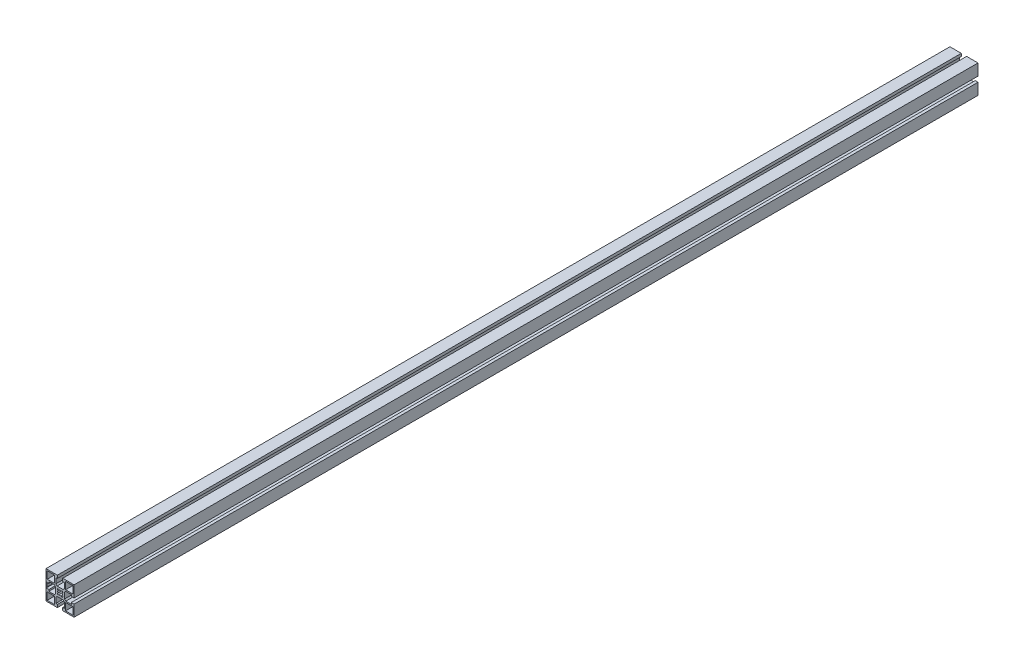
SolidWorks part; units mm, degrees
material "6061 Alloy"
ref_plane "Front Plane" through (0, 0, 0) normal (0, 0, 1) x (1, 0, 0)
ref_plane "Top Plane" through (0, 0, 0) normal (0, 1, 0) x (1, 0, 0)
ref_plane "Right Plane" through (0, 0, 0) normal (1, 0, 0) x (0, 0, -1)
sketch "Sketch1" plane through (0, 0, 0) normal (0, 0, 1) x (1, 0, 0)
  line L0 (-4.2495, 22.1993) -> (-4.2495, 22.4993)
  line L1 (-4.2495, 22.4993) -> (-4.2495, 22.1993)
  line L2 (4.2505, 22.1993) -> (4.2505, 22.4993)
  line L3 (4.2505, 22.4993) -> (4.2505, 22.1993)
  line L4 (-22.1995, 4.2493) -> (-22.4995, 4.2493)
  line L5 (-22.1995, -4.2507) -> (-22.4995, -4.2507)
  line L6 (-4.2495, -22.2007) -> (-4.2495, -22.5007)
  line L7 (4.2505, -22.2007) -> (4.2505, -22.5007)
  line L8 (-22.4995, -22.5007) -> (22.5005, -22.5007)
  line L9 (22.5005, -22.5007) -> (22.5005, 22.4993)
  line L10 (22.5005, 22.4993) -> (-22.4995, 22.4993)
  line L11 (-22.4995, 22.4993) -> (-22.4995, -22.5007)
  line L12 (22.2005, -4.2507) -> (22.5005, -4.2507)
  line L13 (22.2005, 4.2493) -> (22.5005, 4.2493)
  line L24 (-20.4995, -20.5007) -> (-20.4995, -8.8007)
  line L25 (-8.7996, -20.5007) -> (-20.4995, -20.5007)
  line L26 (-8.7996, -8.8007) -> (-8.7996, -20.5007)
  line L27 (-20.4995, -8.8007) -> (-8.7996, -8.8007)
  line L28 (8.8005, -20.5008) -> (8.8005, -8.8008)
  line L29 (20.5005, -20.5008) -> (8.8005, -20.5008)
  line L30 (20.5005, -8.8008) -> (20.5005, -20.5008)
  line L31 (8.8005, -8.8008) -> (20.5005, -8.8008)
  line L32 (20.5006, 8.7993) -> (8.8006, 8.7993)
  line L33 (20.5006, 20.4993) -> (20.5006, 8.7993)
  line L34 (8.8006, 20.4993) -> (20.5006, 20.4993)
  line L35 (8.8006, 8.7993) -> (8.8006, 20.4993)
  line L36 (-8.7995, 20.4993) -> (-8.7995, 8.7993)
  line L37 (-8.7995, 8.7993) -> (-20.4995, 8.7993)
  line L38 (-20.4995, 8.7993) -> (-20.4995, 20.4993)
  line L39 (-20.4995, 20.4993) -> (-8.7995, 20.4993)
  line L54 (-22.1995, -3.9507) -> (-21.7318, -3.483)
  line L55 (-22.1995, -4.2507) -> (-22.1995, -3.9507)
  line L56 (-17.9995, -4.2507) -> (-22.1995, -4.2507)
  line L57 (-17.9995, -6.8007) -> (-17.9995, -4.2507)
  line L58 (-9.1995, -6.8007) -> (-17.9995, -6.8007)
  line L59 (-7.1995, -4.8007) -> (-9.1995, -6.8007)
  line L60 (-7.1995, 4.7993) -> (-7.1995, -4.8007)
  line L61 (-9.1995, 6.7993) -> (-7.1995, 4.7993)
  line L62 (-17.9995, 6.7993) -> (-9.1995, 6.7993)
  line L63 (-17.9995, 4.2493) -> (-17.9995, 6.7993)
  line L64 (-22.1995, 4.2493) -> (-17.9995, 4.2493)
  line L65 (-22.1995, 3.9493) -> (-22.1995, 4.2493)
  line L66 (-21.7317, 3.4815) -> (-22.1995, 3.9493)
  line L67 (-20.9995, -1.7152) -> (-20.9995, 1.7137)
  line L82 (-6.7995, -18.0007) -> (-6.7995, -9.2007)
  line L83 (-4.2495, -18.0007) -> (-6.7995, -18.0007)
  line L84 (-4.2495, -22.2007) -> (-4.2495, -18.0007)
  line L85 (-3.9495, -22.2007) -> (-4.2495, -22.2007)
  line L86 (-3.4817, -21.733) -> (-3.9495, -22.2007)
  line L87 (1.715, -21.0007) -> (-1.7139, -21.0007)
  line L88 (3.9505, -22.2007) -> (3.4828, -21.733)
  line L89 (4.2505, -22.2007) -> (3.9505, -22.2007)
  line L90 (4.2505, -18.0007) -> (4.2505, -22.2007)
  line L91 (6.8005, -18.0007) -> (4.2505, -18.0007)
  line L92 (6.8005, -9.2007) -> (6.8005, -18.0007)
  line L93 (4.8005, -7.2007) -> (6.8005, -9.2007)
  line L94 (-4.7995, -7.2007) -> (4.8005, -7.2007)
  line L95 (-6.7995, -9.2007) -> (-4.7995, -7.2007)
  line L110 (7.2005, -4.8007) -> (7.2005, 4.7993)
  line L111 (9.2005, -6.8007) -> (7.2005, -4.8007)
  line L112 (18.0005, -6.8007) -> (9.2005, -6.8007)
  line L113 (18.0005, -4.2507) -> (18.0005, -6.8007)
  line L114 (22.2005, -4.2507) -> (18.0005, -4.2507)
  line L115 (22.2005, -3.9507) -> (22.2005, -4.2507)
  line L116 (21.7327, -3.4829) -> (22.2005, -3.9507)
  line L117 (21.0005, 1.7138) -> (21.0005, -1.7151)
  line L118 (22.2005, 3.9493) -> (21.7328, 3.4816)
  line L119 (22.2005, 4.2493) -> (22.2005, 3.9493)
  line L120 (18.0005, 4.2493) -> (22.2005, 4.2493)
  line L121 (18.0005, 6.7993) -> (18.0005, 4.2493)
  line L122 (9.2005, 6.7993) -> (18.0005, 6.7993)
  line L123 (7.2005, 4.7993) -> (9.2005, 6.7993)
  line L138 (-4.7995, 7.1993) -> (-6.7995, 9.1993)
  line L139 (4.8005, 7.1993) -> (-4.7995, 7.1993)
  line L140 (6.8005, 9.1993) -> (4.8005, 7.1993)
  line L141 (6.8005, 17.9993) -> (6.8005, 9.1993)
  line L142 (4.2505, 17.9993) -> (6.8005, 17.9993)
  line L143 (4.2505, 22.1993) -> (4.2505, 17.9993)
  line L144 (3.9505, 22.1993) -> (4.2505, 22.1993)
  line L145 (3.4828, 21.7316) -> (3.9505, 22.1993)
  line L146 (-1.7139, 20.9993) -> (1.715, 20.9993)
  line L147 (-3.9495, 22.1993) -> (-3.4817, 21.7315)
  line L148 (-4.2495, 22.1993) -> (-3.9495, 22.1993)
  line L149 (-4.2495, 17.9993) -> (-4.2495, 22.1993)
  line L150 (-6.7995, 17.9993) -> (-4.2495, 17.9993)
  line L151 (-6.7995, 9.1993) -> (-6.7995, 17.9993)
  line L164 (-4.5957, -3.1827) -> (-3.2622, -1.8492)
  line L165 (-3.1815, -4.5969) -> (-4.5957, -3.1827)
  line L166 (-1.848, -3.2635) -> (-3.1815, -4.5969)
  line L167 (3.1825, -4.5969) -> (1.849, -3.2635)
  line L168 (4.5967, -3.1827) -> (3.1825, -4.5969)
  line L169 (3.2633, -1.8492) -> (4.5967, -3.1827)
  line L170 (4.5967, 3.1813) -> (3.2633, 1.8478)
  line L171 (3.1825, 4.5955) -> (4.5967, 3.1813)
  line L172 (1.849, 3.262) -> (3.1825, 4.5955)
  line L173 (-3.1815, 4.5955) -> (-1.848, 3.262)
  line L174 (-4.5957, 3.1813) -> (-3.1815, 4.5955)
  line L175 (-3.2622, 1.8478) -> (-4.5957, 3.1813)
  arc A2 (-21.7318, -3.483) -> (-20.9995, -1.7152) centre (-23.4995, -1.7152) ccw
  arc A3 (-20.9995, 1.7137) -> (-21.7317, 3.4815) centre (-23.4995, 1.7137) ccw
  arc A6 (-1.7139, -21.0007) -> (-3.4817, -21.733) centre (-1.7139, -23.5007) ccw
  arc A7 (3.4828, -21.733) -> (1.715, -21.0007) centre (1.715, -23.5007) ccw
  arc A10 (21.0005, -1.7151) -> (21.7327, -3.4829) centre (23.5005, -1.7151) ccw
  arc A11 (21.7328, 3.4816) -> (21.0005, 1.7138) centre (23.5005, 1.7138) ccw
  arc A14 (1.715, 20.9993) -> (3.4828, 21.7316) centre (1.715, 23.4993) ccw
  arc A15 (-3.4817, 21.7315) -> (-1.7139, 20.9993) centre (-1.7139, 23.4993) ccw
  arc A20 (-1.848, -3.2635) -> (1.849, -3.2635) centre (0.0005, -0.0007) ccw
  arc A21 (3.2633, -1.8492) -> (3.2633, 1.8478) centre (0.0005, -0.0007) ccw
  arc A22 (1.849, 3.262) -> (-1.848, 3.262) centre (0.0005, -0.0007) ccw
  arc A23 (-3.2622, 1.8478) -> (-3.2622, -1.8492) centre (0.0005, -0.0007) ccw
extrude "Boss-Extrude1" add sketch "Sketch1" along normal blind 1447.8 contours L138 L151 L150 L149 L0 L10 L11 L4 L64 L63 L62 L61 L60 L59 L58 L57 L56 L5 L8 L6 L84 L83 L82 L95 L94 L93 L92 L91 L90 L7 L9 L12 L114 L113 L112 L111 L110 L123 L122 L121 L120 L13 L2 L143 L142 L141 L140 | L147 A15 L146 A14 L145 L144 L2 L10 L0 L148 | L67 A3 L66 L65 L4 L11 L5 L55 L54 A2 region at (-4.8859, 20.0993, 0) region at (0.0005, 21.8242, 0) region at (-21.8244, -0.0007, 0)
extrude "Cut-Extrude1" cut sketch "Sketch1<4>" along normal up to next contours L147 A15 L146 A14 L145 L144 L2 L10 L0 L148 region at (0.0005, 21.8242, 0)
sketch "Sketch1<4>" plane through (0, 0, 0) normal (0, 0, 1) x (1, 0, 0) same geometry as "Sketch1"
